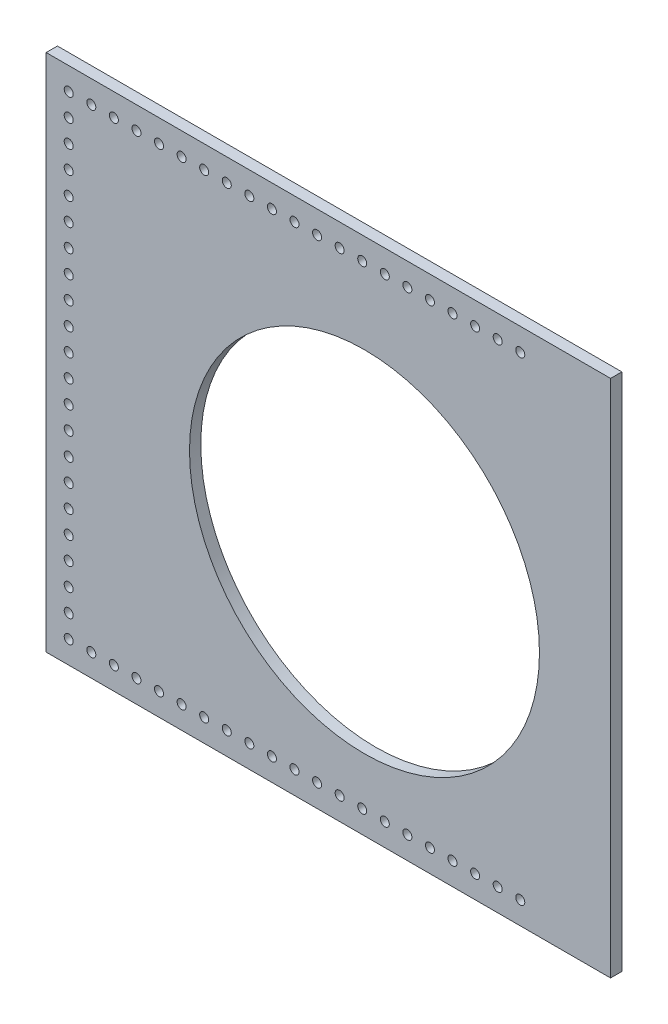
SolidWorks part; units mm, degrees
ref_plane "Front Plane" through (0, 0, 0) normal (0, 0, 1) x (1, 0, 0)
ref_plane "Top Plane" through (0, 0, 0) normal (0, 1, 0) x (1, 0, 0)
ref_plane "Right Plane" through (0, 0, 0) normal (1, 0, 0) x (0, 0, -1)
sketch "Sketch1" plane through (0, 0, 0) normal (0, 0, 1) x (1, 0, 0)
  line L1 (0, 0) -> (317.5, 0)
  line L2 (0, 0) -> (0, 292.1)
  line L4 (317.5, 0) -> (317.5, 292.1)
  line L5 (0, 292.1) -> (317.5, 292.1)
  circle A0 centre (179.07, 138.43) radius 98.425
  circle A1 centre (12.7, 279.4) radius 2.54
  circle A2 centre (25.4, 279.4) radius 2.54
  circle A3 centre (38.1, 279.4) radius 2.54
  circle A4 centre (50.8, 279.4) radius 2.54
  circle A5 centre (63.5, 279.4) radius 2.54
  circle A6 centre (76.2, 279.4) radius 2.54
  circle A7 centre (88.9, 279.4) radius 2.54
  circle A8 centre (101.6, 279.4) radius 2.54
  circle A9 centre (114.3, 279.4) radius 2.54
  circle A10 centre (127, 279.4) radius 2.54
  circle A11 centre (139.7, 279.4) radius 2.54
  circle A12 centre (152.4, 279.4) radius 2.54
  circle A13 centre (165.1, 279.4) radius 2.54
  circle A14 centre (177.8, 279.4) radius 2.54
  circle A15 centre (190.5, 279.4) radius 2.54
  circle A16 centre (203.2, 279.4) radius 2.54
  circle A17 centre (215.9, 279.4) radius 2.54
  circle A18 centre (228.6, 279.4) radius 2.54
  circle A19 centre (241.3, 279.4) radius 2.54
  circle A20 centre (254, 279.4) radius 2.54
  circle A21 centre (266.7, 279.4) radius 2.54
  circle A24 centre (12.7, 266.7) radius 2.54
  circle A25 centre (12.7, 254) radius 2.54
  circle A26 centre (12.7, 241.3) radius 2.54
  circle A27 centre (12.7, 228.6) radius 2.54
  circle A28 centre (12.7, 215.9) radius 2.54
  circle A29 centre (12.7, 203.2) radius 2.54
  circle A30 centre (12.7, 190.5) radius 2.54
  circle A31 centre (12.7, 177.8) radius 2.54
  circle A32 centre (12.7, 165.1) radius 2.54
  circle A33 centre (12.7, 152.4) radius 2.54
  circle A34 centre (12.7, 139.7) radius 2.54
  circle A35 centre (12.7, 127) radius 2.54
  circle A36 centre (12.7, 114.3) radius 2.54
  circle A37 centre (12.7, 101.6) radius 2.54
  circle A38 centre (12.7, 88.9) radius 2.54
  circle A39 centre (12.7, 76.2) radius 2.54
  circle A40 centre (12.7, 63.5) radius 2.54
  circle A41 centre (12.7, 50.8) radius 2.54
  circle A42 centre (12.7, 38.1) radius 2.54
  circle A43 centre (12.7, 25.4) radius 2.54
  circle A44 centre (12.7, 12.7) radius 2.54
  circle A45 centre (25.4, 12.7) radius 2.54
  circle A46 centre (38.1, 12.7) radius 2.54
  circle A47 centre (50.8, 12.7) radius 2.54
  circle A48 centre (63.5, 12.7) radius 2.54
  circle A49 centre (76.2, 12.7) radius 2.54
  circle A50 centre (88.9, 12.7) radius 2.54
  circle A51 centre (101.6, 12.7) radius 2.54
  circle A52 centre (114.3, 12.7) radius 2.54
  circle A53 centre (127, 12.7) radius 2.54
  circle A54 centre (139.7, 12.7) radius 2.54
  circle A55 centre (152.4, 12.7) radius 2.54
  circle A56 centre (165.1, 12.7) radius 2.54
  circle A57 centre (177.8, 12.7) radius 2.54
  circle A58 centre (190.5, 12.7) radius 2.54
  circle A59 centre (203.2, 12.7) radius 2.54
  circle A60 centre (215.9, 12.7) radius 2.54
  circle A61 centre (228.6, 12.7) radius 2.54
  circle A62 centre (241.3, 12.7) radius 2.54
  circle A63 centre (254, 12.7) radius 2.54
  circle A64 centre (266.7, 12.7) radius 2.54
  circle A66 centre (179.07, 138.43) radius 179.07 construction
  dimension "D3" = 196.85
  dimension "D4" = 5.08
  dimension "D5" = 12.7
  dimension "D11" = 12.7
  dimension "D12" = 266.7
  dimension "D14" = 292.1
  dimension "D15" = 358.14
  dimension "D2" = 138.43
  dimension "D6" = 12.7
  dimension "D7" = 317.5
  dimension "D8" = 21
  dimension "D9" = 22
  dimension "D10" = 21
  dimension "D13" = 138.43
extrude "Boss-Extrude1" add sketch "Sketch1" along normal blind 6.35
